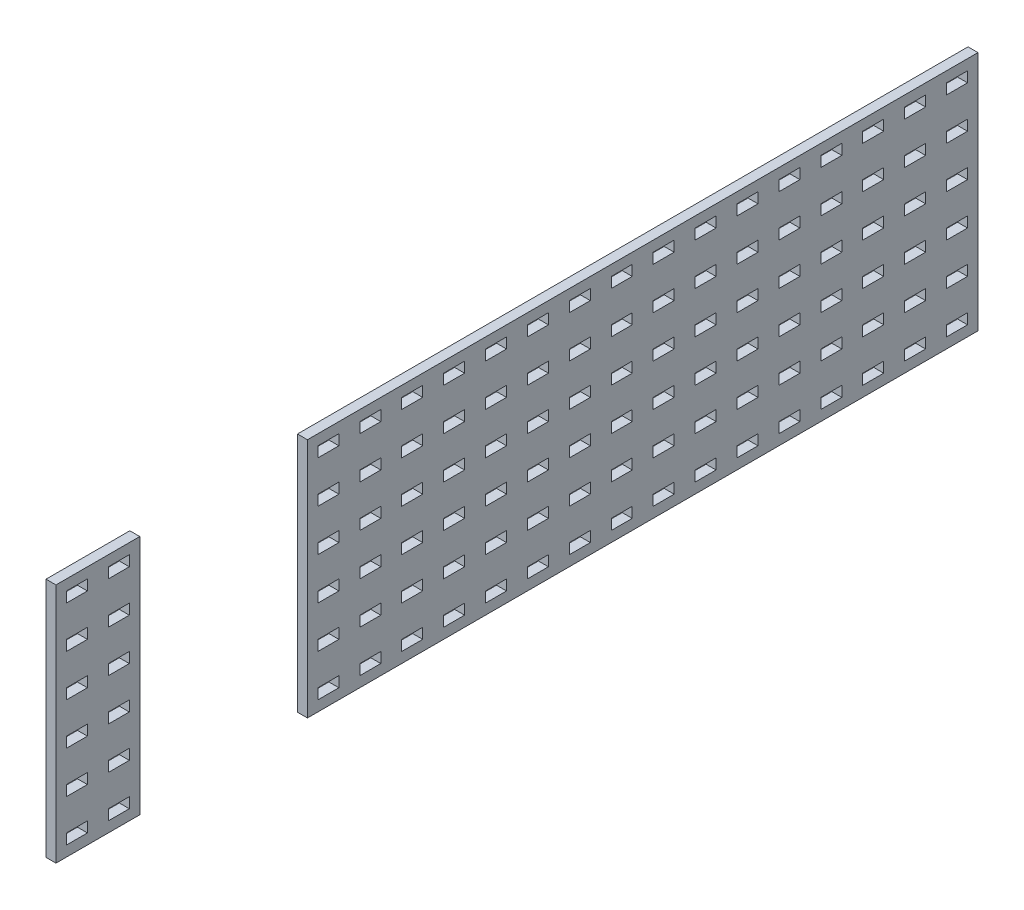
SolidWorks part; units mm, degrees
ref_plane "Front Plane" through (0, 0, 0) normal (0, 0, 1) x (1, 0, 0)
ref_plane "Top Plane" through (0, 0, 0) normal (0, 1, 0) x (1, 0, 0)
ref_plane "Right Plane" through (0, 0, 0) normal (1, 0, 0) x (0, 0, -1)
sketch "Sketch1" plane through (0, 0, 0) normal (1, 0, 0) x (0, 0, -1)
  line L1 (-279.4, -73.025) -> (279.4, -73.025)
  line L2 (-279.4, -73.025) -> (-279.4, 73.025)
  line L3 (-279.4, 73.025) -> (279.4, 73.025)
  line L4 (279.4, -73.025) -> (279.4, 73.025)
  line L5 (-279.4, -73.025) -> (279.4, 73.025) construction
  line L6 (-279.4, 73.025) -> (279.4, -73.025) construction
  point P0 (0, 0)
  dimension "D1" = 558.8
  dimension "D2" = 146.05
extrude "Boss-Extrude1" add sketch "Sketch1" along normal mid plane 6.0452
sketch "Sketch2" plane through (3.0226, 0, 0) normal (1, 0, 0) x (0, 0, -1)
  line L0 (-279.4, -73.025) -> (279.4, -73.025) construction
  line L1 (260.35, -60.325) -> (273.05, -60.325)
  line L2 (260.35, -60.325) -> (260.35, -66.675)
  line L3 (260.35, -66.675) -> (273.05, -66.675)
  line L4 (273.05, -60.325) -> (273.05, -66.675)
  line L5 (260.35, -60.325) -> (273.05, -66.675) construction
  line L6 (260.35, -66.675) -> (273.05, -60.325) construction
  line L7 (279.4, -73.025) -> (279.4, 73.025) construction
  line L8 (234.95, -66.675) -> (247.65, -66.675)
  line L9 (234.95, -60.325) -> (234.95, -66.675)
  line L10 (234.95, -60.325) -> (247.65, -60.325)
  line L11 (247.65, -60.325) -> (247.65, -66.675)
  line L12 (209.55, -66.675) -> (222.25, -66.675)
  line L13 (209.55, -60.325) -> (209.55, -66.675)
  line L14 (209.55, -60.325) -> (222.25, -60.325)
  line L15 (222.25, -60.325) -> (222.25, -66.675)
  line L16 (184.15, -66.675) -> (196.85, -66.675)
  line L17 (184.15, -60.325) -> (184.15, -66.675)
  line L18 (184.15, -60.325) -> (196.85, -60.325)
  line L19 (196.85, -60.325) -> (196.85, -66.675)
  line L20 (158.75, -66.675) -> (171.45, -66.675)
  line L21 (158.75, -60.325) -> (158.75, -66.675)
  line L22 (158.75, -60.325) -> (171.45, -60.325)
  line L23 (171.45, -60.325) -> (171.45, -66.675)
  line L24 (133.35, -66.675) -> (146.05, -66.675)
  line L25 (133.35, -60.325) -> (133.35, -66.675)
  line L26 (133.35, -60.325) -> (146.05, -60.325)
  line L27 (146.05, -60.325) -> (146.05, -66.675)
  line L28 (107.95, -66.675) -> (120.65, -66.675)
  line L29 (107.95, -60.325) -> (107.95, -66.675)
  line L30 (107.95, -60.325) -> (120.65, -60.325)
  line L31 (120.65, -60.325) -> (120.65, -66.675)
  line L32 (82.55, -66.675) -> (95.25, -66.675)
  line L33 (82.55, -60.325) -> (82.55, -66.675)
  line L34 (82.55, -60.325) -> (95.25, -60.325)
  line L35 (95.25, -60.325) -> (95.25, -66.675)
  line L36 (57.15, -66.675) -> (69.85, -66.675)
  line L37 (57.15, -60.325) -> (57.15, -66.675)
  line L38 (57.15, -60.325) -> (69.85, -60.325)
  line L39 (69.85, -60.325) -> (69.85, -66.675)
  line L40 (31.75, -66.675) -> (44.45, -66.675)
  line L41 (31.75, -60.325) -> (31.75, -66.675)
  line L42 (31.75, -60.325) -> (44.45, -60.325)
  line L43 (44.45, -60.325) -> (44.45, -66.675)
  line L44 (6.35, -66.675) -> (19.05, -66.675)
  line L45 (6.35, -60.325) -> (6.35, -66.675)
  line L46 (6.35, -60.325) -> (19.05, -60.325)
  line L47 (19.05, -60.325) -> (19.05, -66.675)
  line L48 (-19.05, -66.675) -> (-6.35, -66.675)
  line L49 (-19.05, -60.325) -> (-19.05, -66.675)
  line L50 (-19.05, -60.325) -> (-6.35, -60.325)
  line L51 (-6.35, -60.325) -> (-6.35, -66.675)
  line L52 (-44.45, -66.675) -> (-31.75, -66.675)
  line L53 (-44.45, -60.325) -> (-44.45, -66.675)
  line L54 (-44.45, -60.325) -> (-31.75, -60.325)
  line L55 (-31.75, -60.325) -> (-31.75, -66.675)
  line L56 (-69.85, -66.675) -> (-57.15, -66.675)
  line L57 (-69.85, -60.325) -> (-69.85, -66.675)
  line L58 (-69.85, -60.325) -> (-57.15, -60.325)
  line L59 (-57.15, -60.325) -> (-57.15, -66.675)
  line L60 (-95.25, -66.675) -> (-82.55, -66.675)
  line L61 (-95.25, -60.325) -> (-95.25, -66.675)
  line L62 (-95.25, -60.325) -> (-82.55, -60.325)
  line L63 (-82.55, -60.325) -> (-82.55, -66.675)
  line L64 (-120.65, -66.675) -> (-107.95, -66.675)
  line L65 (-120.65, -60.325) -> (-120.65, -66.675)
  line L66 (-120.65, -60.325) -> (-107.95, -60.325)
  line L67 (-107.95, -60.325) -> (-107.95, -66.675)
  line L68 (-146.05, -66.675) -> (-133.35, -66.675)
  line L69 (-146.05, -60.325) -> (-146.05, -66.675)
  line L70 (-146.05, -60.325) -> (-133.35, -60.325)
  line L71 (-133.35, -60.325) -> (-133.35, -66.675)
  line L72 (-171.45, -66.675) -> (-158.75, -66.675)
  line L73 (-171.45, -60.325) -> (-171.45, -66.675)
  line L74 (-171.45, -60.325) -> (-158.75, -60.325)
  line L75 (-158.75, -60.325) -> (-158.75, -66.675)
  line L76 (-196.85, -66.675) -> (-184.15, -66.675)
  line L77 (-196.85, -60.325) -> (-196.85, -66.675)
  line L78 (-196.85, -60.325) -> (-184.15, -60.325)
  line L79 (-184.15, -60.325) -> (-184.15, -66.675)
  line L80 (-222.25, -66.675) -> (-209.55, -66.675)
  line L81 (-222.25, -60.325) -> (-222.25, -66.675)
  line L82 (-222.25, -60.325) -> (-209.55, -60.325)
  line L83 (-209.55, -60.325) -> (-209.55, -66.675)
  line L84 (-247.65, -66.675) -> (-234.95, -66.675)
  line L85 (-247.65, -60.325) -> (-247.65, -66.675)
  line L86 (-247.65, -60.325) -> (-234.95, -60.325)
  line L87 (-234.95, -60.325) -> (-234.95, -66.675)
  line L88 (-273.05, -66.675) -> (-260.35, -66.675)
  line L89 (-273.05, -60.325) -> (-273.05, -66.675)
  line L90 (-273.05, -60.325) -> (-260.35, -60.325)
  line L91 (-260.35, -60.325) -> (-260.35, -66.675)
  line L92 (234.95, -41.275) -> (247.65, -41.275)
  line L93 (234.95, -34.925) -> (234.95, -41.275)
  line L94 (234.95, -34.925) -> (247.65, -34.925)
  line L95 (247.65, -34.925) -> (247.65, -41.275)
  line L96 (209.55, -41.275) -> (222.25, -41.275)
  line L97 (209.55, -34.925) -> (209.55, -41.275)
  line L98 (209.55, -34.925) -> (222.25, -34.925)
  line L99 (222.25, -34.925) -> (222.25, -41.275)
  line L100 (184.15, -41.275) -> (196.85, -41.275)
  line L101 (184.15, -34.925) -> (184.15, -41.275)
  line L102 (184.15, -34.925) -> (196.85, -34.925)
  line L103 (196.85, -34.925) -> (196.85, -41.275)
  line L104 (158.75, -41.275) -> (171.45, -41.275)
  line L105 (158.75, -34.925) -> (158.75, -41.275)
  line L106 (158.75, -34.925) -> (171.45, -34.925)
  line L107 (171.45, -34.925) -> (171.45, -41.275)
  line L108 (133.35, -41.275) -> (146.05, -41.275)
  line L109 (133.35, -34.925) -> (133.35, -41.275)
  line L110 (133.35, -34.925) -> (146.05, -34.925)
  line L111 (146.05, -34.925) -> (146.05, -41.275)
  line L112 (107.95, -41.275) -> (120.65, -41.275)
  line L113 (107.95, -34.925) -> (107.95, -41.275)
  line L114 (107.95, -34.925) -> (120.65, -34.925)
  line L115 (120.65, -34.925) -> (120.65, -41.275)
  line L116 (82.55, -41.275) -> (95.25, -41.275)
  line L117 (82.55, -34.925) -> (82.55, -41.275)
  line L118 (82.55, -34.925) -> (95.25, -34.925)
  line L119 (95.25, -34.925) -> (95.25, -41.275)
  line L120 (57.15, -41.275) -> (69.85, -41.275)
  line L121 (57.15, -34.925) -> (57.15, -41.275)
  line L122 (57.15, -34.925) -> (69.85, -34.925)
  line L123 (69.85, -34.925) -> (69.85, -41.275)
  line L124 (31.75, -41.275) -> (44.45, -41.275)
  line L125 (31.75, -34.925) -> (31.75, -41.275)
  line L126 (31.75, -34.925) -> (44.45, -34.925)
  line L127 (44.45, -34.925) -> (44.45, -41.275)
  line L128 (6.35, -41.275) -> (19.05, -41.275)
  line L129 (6.35, -34.925) -> (6.35, -41.275)
  line L130 (6.35, -34.925) -> (19.05, -34.925)
  line L131 (19.05, -34.925) -> (19.05, -41.275)
  line L132 (-19.05, -41.275) -> (-6.35, -41.275)
  line L133 (-19.05, -34.925) -> (-19.05, -41.275)
  line L134 (-19.05, -34.925) -> (-6.35, -34.925)
  line L135 (-6.35, -34.925) -> (-6.35, -41.275)
  line L136 (-44.45, -41.275) -> (-31.75, -41.275)
  line L137 (-44.45, -34.925) -> (-44.45, -41.275)
  line L138 (-44.45, -34.925) -> (-31.75, -34.925)
  line L139 (-31.75, -34.925) -> (-31.75, -41.275)
  line L140 (-69.85, -41.275) -> (-57.15, -41.275)
  line L141 (-69.85, -34.925) -> (-69.85, -41.275)
  line L142 (-69.85, -34.925) -> (-57.15, -34.925)
  line L143 (-57.15, -34.925) -> (-57.15, -41.275)
  line L144 (-95.25, -41.275) -> (-82.55, -41.275)
  line L145 (-95.25, -34.925) -> (-95.25, -41.275)
  line L146 (-95.25, -34.925) -> (-82.55, -34.925)
  line L147 (-82.55, -34.925) -> (-82.55, -41.275)
  line L148 (-120.65, -41.275) -> (-107.95, -41.275)
  line L149 (-120.65, -34.925) -> (-120.65, -41.275)
  line L150 (-120.65, -34.925) -> (-107.95, -34.925)
  line L151 (-107.95, -34.925) -> (-107.95, -41.275)
  line L152 (-146.05, -41.275) -> (-133.35, -41.275)
  line L153 (-146.05, -34.925) -> (-146.05, -41.275)
  line L154 (-146.05, -34.925) -> (-133.35, -34.925)
  line L155 (-133.35, -34.925) -> (-133.35, -41.275)
  line L156 (-171.45, -41.275) -> (-158.75, -41.275)
  line L157 (-171.45, -34.925) -> (-171.45, -41.275)
  line L158 (-171.45, -34.925) -> (-158.75, -34.925)
  line L159 (-158.75, -34.925) -> (-158.75, -41.275)
  line L160 (-196.85, -41.275) -> (-184.15, -41.275)
  line L161 (-196.85, -34.925) -> (-196.85, -41.275)
  line L162 (-196.85, -34.925) -> (-184.15, -34.925)
  line L163 (-184.15, -34.925) -> (-184.15, -41.275)
  line L164 (-222.25, -41.275) -> (-209.55, -41.275)
  line L165 (-222.25, -34.925) -> (-222.25, -41.275)
  line L166 (-222.25, -34.925) -> (-209.55, -34.925)
  line L167 (-209.55, -34.925) -> (-209.55, -41.275)
  line L168 (-247.65, -41.275) -> (-234.95, -41.275)
  line L169 (-247.65, -34.925) -> (-247.65, -41.275)
  line L170 (-247.65, -34.925) -> (-234.95, -34.925)
  line L171 (-234.95, -34.925) -> (-234.95, -41.275)
  line L172 (-273.05, -41.275) -> (-260.35, -41.275)
  line L173 (-273.05, -34.925) -> (-273.05, -41.275)
  line L174 (-273.05, -34.925) -> (-260.35, -34.925)
  line L175 (-260.35, -34.925) -> (-260.35, -41.275)
  line L176 (234.95, -15.875) -> (247.65, -15.875)
  line L177 (234.95, -9.525) -> (234.95, -15.875)
  line L178 (234.95, -9.525) -> (247.65, -9.525)
  line L179 (247.65, -9.525) -> (247.65, -15.875)
  line L180 (209.55, -15.875) -> (222.25, -15.875)
  line L181 (209.55, -9.525) -> (209.55, -15.875)
  line L182 (209.55, -9.525) -> (222.25, -9.525)
  line L183 (222.25, -9.525) -> (222.25, -15.875)
  line L184 (184.15, -15.875) -> (196.85, -15.875)
  line L185 (184.15, -9.525) -> (184.15, -15.875)
  line L186 (184.15, -9.525) -> (196.85, -9.525)
  line L187 (196.85, -9.525) -> (196.85, -15.875)
  line L188 (158.75, -15.875) -> (171.45, -15.875)
  line L189 (158.75, -9.525) -> (158.75, -15.875)
  line L190 (158.75, -9.525) -> (171.45, -9.525)
  line L191 (171.45, -9.525) -> (171.45, -15.875)
  line L192 (133.35, -15.875) -> (146.05, -15.875)
  line L193 (133.35, -9.525) -> (133.35, -15.875)
  line L194 (133.35, -9.525) -> (146.05, -9.525)
  line L195 (146.05, -9.525) -> (146.05, -15.875)
  line L196 (107.95, -15.875) -> (120.65, -15.875)
  line L197 (107.95, -9.525) -> (107.95, -15.875)
  line L198 (107.95, -9.525) -> (120.65, -9.525)
  line L199 (120.65, -9.525) -> (120.65, -15.875)
  line L200 (82.55, -15.875) -> (95.25, -15.875)
  line L201 (82.55, -9.525) -> (82.55, -15.875)
  line L202 (82.55, -9.525) -> (95.25, -9.525)
  line L203 (95.25, -9.525) -> (95.25, -15.875)
  line L204 (57.15, -15.875) -> (69.85, -15.875)
  line L205 (57.15, -9.525) -> (57.15, -15.875)
  line L206 (57.15, -9.525) -> (69.85, -9.525)
  line L207 (69.85, -9.525) -> (69.85, -15.875)
  line L208 (31.75, -15.875) -> (44.45, -15.875)
  line L209 (31.75, -9.525) -> (31.75, -15.875)
  line L210 (31.75, -9.525) -> (44.45, -9.525)
  line L211 (44.45, -9.525) -> (44.45, -15.875)
  line L212 (6.35, -15.875) -> (19.05, -15.875)
  line L213 (6.35, -9.525) -> (6.35, -15.875)
  line L214 (6.35, -9.525) -> (19.05, -9.525)
  line L215 (19.05, -9.525) -> (19.05, -15.875)
  line L216 (-19.05, -15.875) -> (-6.35, -15.875)
  line L217 (-19.05, -9.525) -> (-19.05, -15.875)
  line L218 (-19.05, -9.525) -> (-6.35, -9.525)
  line L219 (-6.35, -9.525) -> (-6.35, -15.875)
  line L220 (-44.45, -15.875) -> (-31.75, -15.875)
  line L221 (-44.45, -9.525) -> (-44.45, -15.875)
  line L222 (-44.45, -9.525) -> (-31.75, -9.525)
  line L223 (-31.75, -9.525) -> (-31.75, -15.875)
  line L224 (-69.85, -15.875) -> (-57.15, -15.875)
  line L225 (-69.85, -9.525) -> (-69.85, -15.875)
  line L226 (-69.85, -9.525) -> (-57.15, -9.525)
  line L227 (-57.15, -9.525) -> (-57.15, -15.875)
  line L228 (-95.25, -15.875) -> (-82.55, -15.875)
  line L229 (-95.25, -9.525) -> (-95.25, -15.875)
  line L230 (-95.25, -9.525) -> (-82.55, -9.525)
  line L231 (-82.55, -9.525) -> (-82.55, -15.875)
  line L232 (-120.65, -15.875) -> (-107.95, -15.875)
  line L233 (-120.65, -9.525) -> (-120.65, -15.875)
  line L234 (-120.65, -9.525) -> (-107.95, -9.525)
  line L235 (-107.95, -9.525) -> (-107.95, -15.875)
  line L236 (-146.05, -15.875) -> (-133.35, -15.875)
  line L237 (-146.05, -9.525) -> (-146.05, -15.875)
  line L238 (-146.05, -9.525) -> (-133.35, -9.525)
  line L239 (-133.35, -9.525) -> (-133.35, -15.875)
  line L240 (-171.45, -15.875) -> (-158.75, -15.875)
  line L241 (-171.45, -9.525) -> (-171.45, -15.875)
  line L242 (-171.45, -9.525) -> (-158.75, -9.525)
  line L243 (-158.75, -9.525) -> (-158.75, -15.875)
  line L244 (-196.85, -15.875) -> (-184.15, -15.875)
  line L245 (-196.85, -9.525) -> (-196.85, -15.875)
  line L246 (-196.85, -9.525) -> (-184.15, -9.525)
  line L247 (-184.15, -9.525) -> (-184.15, -15.875)
  line L248 (-222.25, -15.875) -> (-209.55, -15.875)
  line L249 (-222.25, -9.525) -> (-222.25, -15.875)
  line L250 (-222.25, -9.525) -> (-209.55, -9.525)
  line L251 (-209.55, -9.525) -> (-209.55, -15.875)
  line L252 (-247.65, -15.875) -> (-234.95, -15.875)
  line L253 (-247.65, -9.525) -> (-247.65, -15.875)
  line L254 (-247.65, -9.525) -> (-234.95, -9.525)
  line L255 (-234.95, -9.525) -> (-234.95, -15.875)
  line L256 (-273.05, -15.875) -> (-260.35, -15.875)
  line L257 (-273.05, -9.525) -> (-273.05, -15.875)
  line L258 (-273.05, -9.525) -> (-260.35, -9.525)
  line L259 (-260.35, -9.525) -> (-260.35, -15.875)
  line L260 (234.95, 9.525) -> (247.65, 9.525)
  line L261 (234.95, 15.875) -> (234.95, 9.525)
  line L262 (234.95, 15.875) -> (247.65, 15.875)
  line L263 (247.65, 15.875) -> (247.65, 9.525)
  line L264 (209.55, 9.525) -> (222.25, 9.525)
  line L265 (209.55, 15.875) -> (209.55, 9.525)
  line L266 (209.55, 15.875) -> (222.25, 15.875)
  line L267 (222.25, 15.875) -> (222.25, 9.525)
  line L268 (184.15, 9.525) -> (196.85, 9.525)
  line L269 (184.15, 15.875) -> (184.15, 9.525)
  line L270 (184.15, 15.875) -> (196.85, 15.875)
  line L271 (196.85, 15.875) -> (196.85, 9.525)
  line L272 (158.75, 9.525) -> (171.45, 9.525)
  line L273 (158.75, 15.875) -> (158.75, 9.525)
  line L274 (158.75, 15.875) -> (171.45, 15.875)
  line L275 (171.45, 15.875) -> (171.45, 9.525)
  line L276 (133.35, 9.525) -> (146.05, 9.525)
  line L277 (133.35, 15.875) -> (133.35, 9.525)
  line L278 (133.35, 15.875) -> (146.05, 15.875)
  line L279 (146.05, 15.875) -> (146.05, 9.525)
  line L280 (107.95, 9.525) -> (120.65, 9.525)
  line L281 (107.95, 15.875) -> (107.95, 9.525)
  line L282 (107.95, 15.875) -> (120.65, 15.875)
  line L283 (120.65, 15.875) -> (120.65, 9.525)
  line L284 (82.55, 9.525) -> (95.25, 9.525)
  line L285 (82.55, 15.875) -> (82.55, 9.525)
  line L286 (82.55, 15.875) -> (95.25, 15.875)
  line L287 (95.25, 15.875) -> (95.25, 9.525)
  line L288 (57.15, 9.525) -> (69.85, 9.525)
  line L289 (57.15, 15.875) -> (57.15, 9.525)
  line L290 (57.15, 15.875) -> (69.85, 15.875)
  line L291 (69.85, 15.875) -> (69.85, 9.525)
  line L292 (31.75, 9.525) -> (44.45, 9.525)
  line L293 (31.75, 15.875) -> (31.75, 9.525)
  line L294 (31.75, 15.875) -> (44.45, 15.875)
  line L295 (44.45, 15.875) -> (44.45, 9.525)
  line L296 (6.35, 9.525) -> (19.05, 9.525)
  line L297 (6.35, 15.875) -> (6.35, 9.525)
  line L298 (6.35, 15.875) -> (19.05, 15.875)
  line L299 (19.05, 15.875) -> (19.05, 9.525)
  line L300 (-19.05, 9.525) -> (-6.35, 9.525)
  line L301 (-19.05, 15.875) -> (-19.05, 9.525)
  line L302 (-19.05, 15.875) -> (-6.35, 15.875)
  line L303 (-6.35, 15.875) -> (-6.35, 9.525)
  line L304 (-44.45, 9.525) -> (-31.75, 9.525)
  line L305 (-44.45, 15.875) -> (-44.45, 9.525)
  line L306 (-44.45, 15.875) -> (-31.75, 15.875)
  line L307 (-31.75, 15.875) -> (-31.75, 9.525)
  line L308 (-69.85, 9.525) -> (-57.15, 9.525)
  line L309 (-69.85, 15.875) -> (-69.85, 9.525)
  line L310 (-69.85, 15.875) -> (-57.15, 15.875)
  line L311 (-57.15, 15.875) -> (-57.15, 9.525)
  line L312 (-95.25, 9.525) -> (-82.55, 9.525)
  line L313 (-95.25, 15.875) -> (-95.25, 9.525)
  line L314 (-95.25, 15.875) -> (-82.55, 15.875)
  line L315 (-82.55, 15.875) -> (-82.55, 9.525)
  line L316 (-120.65, 9.525) -> (-107.95, 9.525)
  line L317 (-120.65, 15.875) -> (-120.65, 9.525)
  line L318 (-120.65, 15.875) -> (-107.95, 15.875)
  line L319 (-107.95, 15.875) -> (-107.95, 9.525)
  line L320 (-146.05, 9.525) -> (-133.35, 9.525)
  line L321 (-146.05, 15.875) -> (-146.05, 9.525)
  line L322 (-146.05, 15.875) -> (-133.35, 15.875)
  line L323 (-133.35, 15.875) -> (-133.35, 9.525)
  line L324 (-171.45, 9.525) -> (-158.75, 9.525)
  line L325 (-171.45, 15.875) -> (-171.45, 9.525)
  line L326 (-171.45, 15.875) -> (-158.75, 15.875)
  line L327 (-158.75, 15.875) -> (-158.75, 9.525)
  line L328 (-196.85, 9.525) -> (-184.15, 9.525)
  line L329 (-196.85, 15.875) -> (-196.85, 9.525)
  line L330 (-196.85, 15.875) -> (-184.15, 15.875)
  line L331 (-184.15, 15.875) -> (-184.15, 9.525)
  line L332 (-222.25, 9.525) -> (-209.55, 9.525)
  line L333 (-222.25, 15.875) -> (-222.25, 9.525)
  line L334 (-222.25, 15.875) -> (-209.55, 15.875)
  line L335 (-209.55, 15.875) -> (-209.55, 9.525)
  line L336 (-247.65, 9.525) -> (-234.95, 9.525)
  line L337 (-247.65, 15.875) -> (-247.65, 9.525)
  line L338 (-247.65, 15.875) -> (-234.95, 15.875)
  line L339 (-234.95, 15.875) -> (-234.95, 9.525)
  line L340 (-273.05, 9.525) -> (-260.35, 9.525)
  line L341 (-273.05, 15.875) -> (-273.05, 9.525)
  line L342 (-273.05, 15.875) -> (-260.35, 15.875)
  line L343 (-260.35, 15.875) -> (-260.35, 9.525)
  line L344 (234.95, 34.925) -> (247.65, 34.925)
  line L345 (234.95, 41.275) -> (234.95, 34.925)
  line L346 (234.95, 41.275) -> (247.65, 41.275)
  line L347 (247.65, 41.275) -> (247.65, 34.925)
  line L348 (209.55, 34.925) -> (222.25, 34.925)
  line L349 (209.55, 41.275) -> (209.55, 34.925)
  line L350 (209.55, 41.275) -> (222.25, 41.275)
  line L351 (222.25, 41.275) -> (222.25, 34.925)
  line L352 (184.15, 34.925) -> (196.85, 34.925)
  line L353 (184.15, 41.275) -> (184.15, 34.925)
  line L354 (184.15, 41.275) -> (196.85, 41.275)
  line L355 (196.85, 41.275) -> (196.85, 34.925)
  line L356 (158.75, 34.925) -> (171.45, 34.925)
  line L357 (158.75, 41.275) -> (158.75, 34.925)
  line L358 (158.75, 41.275) -> (171.45, 41.275)
  line L359 (171.45, 41.275) -> (171.45, 34.925)
  line L360 (133.35, 34.925) -> (146.05, 34.925)
  line L361 (133.35, 41.275) -> (133.35, 34.925)
  line L362 (133.35, 41.275) -> (146.05, 41.275)
  line L363 (146.05, 41.275) -> (146.05, 34.925)
  line L364 (107.95, 34.925) -> (120.65, 34.925)
  line L365 (107.95, 41.275) -> (107.95, 34.925)
  line L366 (107.95, 41.275) -> (120.65, 41.275)
  line L367 (120.65, 41.275) -> (120.65, 34.925)
  line L368 (82.55, 34.925) -> (95.25, 34.925)
  line L369 (82.55, 41.275) -> (82.55, 34.925)
  line L370 (82.55, 41.275) -> (95.25, 41.275)
  line L371 (95.25, 41.275) -> (95.25, 34.925)
  line L372 (57.15, 34.925) -> (69.85, 34.925)
  line L373 (57.15, 41.275) -> (57.15, 34.925)
  line L374 (57.15, 41.275) -> (69.85, 41.275)
  line L375 (69.85, 41.275) -> (69.85, 34.925)
  line L376 (31.75, 34.925) -> (44.45, 34.925)
  line L377 (31.75, 41.275) -> (31.75, 34.925)
  line L378 (31.75, 41.275) -> (44.45, 41.275)
  line L379 (44.45, 41.275) -> (44.45, 34.925)
  line L380 (6.35, 34.925) -> (19.05, 34.925)
  line L381 (6.35, 41.275) -> (6.35, 34.925)
  line L382 (6.35, 41.275) -> (19.05, 41.275)
  line L383 (19.05, 41.275) -> (19.05, 34.925)
  line L384 (-19.05, 34.925) -> (-6.35, 34.925)
  line L385 (-19.05, 41.275) -> (-19.05, 34.925)
  line L386 (-19.05, 41.275) -> (-6.35, 41.275)
  line L387 (-6.35, 41.275) -> (-6.35, 34.925)
  line L388 (-44.45, 34.925) -> (-31.75, 34.925)
  line L389 (-44.45, 41.275) -> (-44.45, 34.925)
  line L390 (-44.45, 41.275) -> (-31.75, 41.275)
  line L391 (-31.75, 41.275) -> (-31.75, 34.925)
  line L392 (-69.85, 34.925) -> (-57.15, 34.925)
  line L393 (-69.85, 41.275) -> (-69.85, 34.925)
  line L394 (-69.85, 41.275) -> (-57.15, 41.275)
  line L395 (-57.15, 41.275) -> (-57.15, 34.925)
  line L396 (-95.25, 34.925) -> (-82.55, 34.925)
  line L397 (-95.25, 41.275) -> (-95.25, 34.925)
  line L398 (-95.25, 41.275) -> (-82.55, 41.275)
  line L399 (-82.55, 41.275) -> (-82.55, 34.925)
  line L400 (-120.65, 34.925) -> (-107.95, 34.925)
  line L401 (-120.65, 41.275) -> (-120.65, 34.925)
  line L402 (-120.65, 41.275) -> (-107.95, 41.275)
  line L403 (-107.95, 41.275) -> (-107.95, 34.925)
  line L404 (-146.05, 34.925) -> (-133.35, 34.925)
  line L405 (-146.05, 41.275) -> (-146.05, 34.925)
  line L406 (-146.05, 41.275) -> (-133.35, 41.275)
  line L407 (-133.35, 41.275) -> (-133.35, 34.925)
  line L408 (-171.45, 34.925) -> (-158.75, 34.925)
  line L409 (-171.45, 41.275) -> (-171.45, 34.925)
  line L410 (-171.45, 41.275) -> (-158.75, 41.275)
  line L411 (-158.75, 41.275) -> (-158.75, 34.925)
  line L412 (-196.85, 34.925) -> (-184.15, 34.925)
  line L413 (-196.85, 41.275) -> (-196.85, 34.925)
  line L414 (-196.85, 41.275) -> (-184.15, 41.275)
  line L415 (-184.15, 41.275) -> (-184.15, 34.925)
  line L416 (-222.25, 34.925) -> (-209.55, 34.925)
  line L417 (-222.25, 41.275) -> (-222.25, 34.925)
  line L418 (-222.25, 41.275) -> (-209.55, 41.275)
  line L419 (-209.55, 41.275) -> (-209.55, 34.925)
  line L420 (-247.65, 34.925) -> (-234.95, 34.925)
  line L421 (-247.65, 41.275) -> (-247.65, 34.925)
  line L422 (-247.65, 41.275) -> (-234.95, 41.275)
  line L423 (-234.95, 41.275) -> (-234.95, 34.925)
  line L424 (-273.05, 34.925) -> (-260.35, 34.925)
  line L425 (-273.05, 41.275) -> (-273.05, 34.925)
  line L426 (-273.05, 41.275) -> (-260.35, 41.275)
  line L427 (-260.35, 41.275) -> (-260.35, 34.925)
  line L428 (234.95, 60.325) -> (247.65, 60.325)
  line L429 (234.95, 66.675) -> (234.95, 60.325)
  line L430 (234.95, 66.675) -> (247.65, 66.675)
  line L431 (247.65, 66.675) -> (247.65, 60.325)
  line L432 (209.55, 60.325) -> (222.25, 60.325)
  line L433 (209.55, 66.675) -> (209.55, 60.325)
  line L434 (209.55, 66.675) -> (222.25, 66.675)
  line L435 (222.25, 66.675) -> (222.25, 60.325)
  line L436 (184.15, 60.325) -> (196.85, 60.325)
  line L437 (184.15, 66.675) -> (184.15, 60.325)
  line L438 (184.15, 66.675) -> (196.85, 66.675)
  line L439 (196.85, 66.675) -> (196.85, 60.325)
  line L440 (158.75, 60.325) -> (171.45, 60.325)
  line L441 (158.75, 66.675) -> (158.75, 60.325)
  line L442 (158.75, 66.675) -> (171.45, 66.675)
  line L443 (171.45, 66.675) -> (171.45, 60.325)
  line L444 (133.35, 60.325) -> (146.05, 60.325)
  line L445 (133.35, 66.675) -> (133.35, 60.325)
  line L446 (133.35, 66.675) -> (146.05, 66.675)
  line L447 (146.05, 66.675) -> (146.05, 60.325)
  line L448 (107.95, 60.325) -> (120.65, 60.325)
  line L449 (107.95, 66.675) -> (107.95, 60.325)
  line L450 (107.95, 66.675) -> (120.65, 66.675)
  line L451 (120.65, 66.675) -> (120.65, 60.325)
  line L452 (82.55, 60.325) -> (95.25, 60.325)
  line L453 (82.55, 66.675) -> (82.55, 60.325)
  line L454 (82.55, 66.675) -> (95.25, 66.675)
  line L455 (95.25, 66.675) -> (95.25, 60.325)
  line L456 (57.15, 60.325) -> (69.85, 60.325)
  line L457 (57.15, 66.675) -> (57.15, 60.325)
  line L458 (57.15, 66.675) -> (69.85, 66.675)
  line L459 (69.85, 66.675) -> (69.85, 60.325)
  line L460 (31.75, 60.325) -> (44.45, 60.325)
  line L461 (31.75, 66.675) -> (31.75, 60.325)
  line L462 (31.75, 66.675) -> (44.45, 66.675)
  line L463 (44.45, 66.675) -> (44.45, 60.325)
  line L464 (6.35, 60.325) -> (19.05, 60.325)
  line L465 (6.35, 66.675) -> (6.35, 60.325)
  line L466 (6.35, 66.675) -> (19.05, 66.675)
  line L467 (19.05, 66.675) -> (19.05, 60.325)
  line L468 (-19.05, 60.325) -> (-6.35, 60.325)
  line L469 (-19.05, 66.675) -> (-19.05, 60.325)
  line L470 (-19.05, 66.675) -> (-6.35, 66.675)
  line L471 (-6.35, 66.675) -> (-6.35, 60.325)
  line L472 (-44.45, 60.325) -> (-31.75, 60.325)
  line L473 (-44.45, 66.675) -> (-44.45, 60.325)
  line L474 (-44.45, 66.675) -> (-31.75, 66.675)
  line L475 (-31.75, 66.675) -> (-31.75, 60.325)
  line L476 (-69.85, 60.325) -> (-57.15, 60.325)
  line L477 (-69.85, 66.675) -> (-69.85, 60.325)
  line L478 (-69.85, 66.675) -> (-57.15, 66.675)
  line L479 (-57.15, 66.675) -> (-57.15, 60.325)
  line L480 (-95.25, 60.325) -> (-82.55, 60.325)
  line L481 (-95.25, 66.675) -> (-95.25, 60.325)
  line L482 (-95.25, 66.675) -> (-82.55, 66.675)
  line L483 (-82.55, 66.675) -> (-82.55, 60.325)
  line L484 (-120.65, 60.325) -> (-107.95, 60.325)
  line L485 (-120.65, 66.675) -> (-120.65, 60.325)
  line L486 (-120.65, 66.675) -> (-107.95, 66.675)
  line L487 (-107.95, 66.675) -> (-107.95, 60.325)
  line L488 (-146.05, 60.325) -> (-133.35, 60.325)
  line L489 (-146.05, 66.675) -> (-146.05, 60.325)
  line L490 (-146.05, 66.675) -> (-133.35, 66.675)
  line L491 (-133.35, 66.675) -> (-133.35, 60.325)
  line L492 (-171.45, 60.325) -> (-158.75, 60.325)
  line L493 (-171.45, 66.675) -> (-171.45, 60.325)
  line L494 (-171.45, 66.675) -> (-158.75, 66.675)
  line L495 (-158.75, 66.675) -> (-158.75, 60.325)
  line L496 (-196.85, 60.325) -> (-184.15, 60.325)
  line L497 (-196.85, 66.675) -> (-196.85, 60.325)
  line L498 (-196.85, 66.675) -> (-184.15, 66.675)
  line L499 (-184.15, 66.675) -> (-184.15, 60.325)
  line L500 (-222.25, 60.325) -> (-209.55, 60.325)
  line L501 (-222.25, 66.675) -> (-222.25, 60.325)
  line L502 (-222.25, 66.675) -> (-209.55, 66.675)
  line L503 (-209.55, 66.675) -> (-209.55, 60.325)
  line L504 (-247.65, 60.325) -> (-234.95, 60.325)
  line L505 (-247.65, 66.675) -> (-247.65, 60.325)
  line L506 (-247.65, 66.675) -> (-234.95, 66.675)
  line L507 (-234.95, 66.675) -> (-234.95, 60.325)
  line L508 (-273.05, 60.325) -> (-260.35, 60.325)
  line L509 (-273.05, 66.675) -> (-273.05, 60.325)
  line L510 (-273.05, 66.675) -> (-260.35, 66.675)
  line L511 (-260.35, 66.675) -> (-260.35, 60.325)
  line L512 (234.95, 85.725) -> (247.65, 85.725)
  line L513 (234.95, 92.075) -> (234.95, 85.725)
  line L514 (234.95, 92.075) -> (247.65, 92.075)
  line L515 (247.65, 92.075) -> (247.65, 85.725)
  line L516 (209.55, 85.725) -> (222.25, 85.725)
  line L517 (209.55, 92.075) -> (209.55, 85.725)
  line L518 (209.55, 92.075) -> (222.25, 92.075)
  line L519 (222.25, 92.075) -> (222.25, 85.725)
  line L520 (184.15, 85.725) -> (196.85, 85.725)
  line L521 (184.15, 92.075) -> (184.15, 85.725)
  line L522 (184.15, 92.075) -> (196.85, 92.075)
  line L523 (196.85, 92.075) -> (196.85, 85.725)
  line L524 (158.75, 85.725) -> (171.45, 85.725)
  line L525 (158.75, 92.075) -> (158.75, 85.725)
  line L526 (158.75, 92.075) -> (171.45, 92.075)
  line L527 (171.45, 92.075) -> (171.45, 85.725)
  line L528 (133.35, 85.725) -> (146.05, 85.725)
  line L529 (133.35, 92.075) -> (133.35, 85.725)
  line L530 (133.35, 92.075) -> (146.05, 92.075)
  line L531 (146.05, 92.075) -> (146.05, 85.725)
  line L532 (107.95, 85.725) -> (120.65, 85.725)
  line L533 (107.95, 92.075) -> (107.95, 85.725)
  line L534 (107.95, 92.075) -> (120.65, 92.075)
  line L535 (120.65, 92.075) -> (120.65, 85.725)
  line L536 (82.55, 85.725) -> (95.25, 85.725)
  line L537 (82.55, 92.075) -> (82.55, 85.725)
  line L538 (82.55, 92.075) -> (95.25, 92.075)
  line L539 (95.25, 92.075) -> (95.25, 85.725)
  line L540 (57.15, 85.725) -> (69.85, 85.725)
  line L541 (57.15, 92.075) -> (57.15, 85.725)
  line L542 (57.15, 92.075) -> (69.85, 92.075)
  line L543 (69.85, 92.075) -> (69.85, 85.725)
  line L544 (31.75, 85.725) -> (44.45, 85.725)
  line L545 (31.75, 92.075) -> (31.75, 85.725)
  line L546 (31.75, 92.075) -> (44.45, 92.075)
  line L547 (44.45, 92.075) -> (44.45, 85.725)
  line L548 (6.35, 85.725) -> (19.05, 85.725)
  line L549 (6.35, 92.075) -> (6.35, 85.725)
  line L550 (6.35, 92.075) -> (19.05, 92.075)
  line L551 (19.05, 92.075) -> (19.05, 85.725)
  line L552 (-19.05, 85.725) -> (-6.35, 85.725)
  line L553 (-19.05, 92.075) -> (-19.05, 85.725)
  line L554 (-19.05, 92.075) -> (-6.35, 92.075)
  line L555 (-6.35, 92.075) -> (-6.35, 85.725)
  line L556 (-44.45, 85.725) -> (-31.75, 85.725)
  line L557 (-44.45, 92.075) -> (-44.45, 85.725)
  line L558 (-44.45, 92.075) -> (-31.75, 92.075)
  line L559 (-31.75, 92.075) -> (-31.75, 85.725)
  line L560 (-69.85, 85.725) -> (-57.15, 85.725)
  line L561 (-69.85, 92.075) -> (-69.85, 85.725)
  line L562 (-69.85, 92.075) -> (-57.15, 92.075)
  line L563 (-57.15, 92.075) -> (-57.15, 85.725)
  line L564 (-95.25, 85.725) -> (-82.55, 85.725)
  line L565 (-95.25, 92.075) -> (-95.25, 85.725)
  line L566 (-95.25, 92.075) -> (-82.55, 92.075)
  line L567 (-82.55, 92.075) -> (-82.55, 85.725)
  line L568 (-120.65, 85.725) -> (-107.95, 85.725)
  line L569 (-120.65, 92.075) -> (-120.65, 85.725)
  line L570 (-120.65, 92.075) -> (-107.95, 92.075)
  line L571 (-107.95, 92.075) -> (-107.95, 85.725)
  line L572 (-146.05, 85.725) -> (-133.35, 85.725)
  line L573 (-146.05, 92.075) -> (-146.05, 85.725)
  line L574 (-146.05, 92.075) -> (-133.35, 92.075)
  line L575 (-133.35, 92.075) -> (-133.35, 85.725)
  line L576 (-171.45, 85.725) -> (-158.75, 85.725)
  line L577 (-171.45, 92.075) -> (-171.45, 85.725)
  line L578 (-171.45, 92.075) -> (-158.75, 92.075)
  line L579 (-158.75, 92.075) -> (-158.75, 85.725)
  line L580 (-196.85, 85.725) -> (-184.15, 85.725)
  line L581 (-196.85, 92.075) -> (-196.85, 85.725)
  line L582 (-196.85, 92.075) -> (-184.15, 92.075)
  line L583 (-184.15, 92.075) -> (-184.15, 85.725)
  line L584 (-222.25, 85.725) -> (-209.55, 85.725)
  line L585 (-222.25, 92.075) -> (-222.25, 85.725)
  line L586 (-222.25, 92.075) -> (-209.55, 92.075)
  line L587 (-209.55, 92.075) -> (-209.55, 85.725)
  line L588 (-247.65, 85.725) -> (-234.95, 85.725)
  line L589 (-247.65, 92.075) -> (-247.65, 85.725)
  line L590 (-247.65, 92.075) -> (-234.95, 92.075)
  line L591 (-234.95, 92.075) -> (-234.95, 85.725)
  line L592 (-273.05, 85.725) -> (-260.35, 85.725)
  line L593 (-273.05, 92.075) -> (-273.05, 85.725)
  line L594 (-273.05, 92.075) -> (-260.35, 92.075)
  line L595 (-260.35, 92.075) -> (-260.35, 85.725)
  line L596 (234.95, 111.125) -> (247.65, 111.125)
  line L597 (234.95, 117.475) -> (234.95, 111.125)
  line L598 (234.95, 117.475) -> (247.65, 117.475)
  line L599 (247.65, 117.475) -> (247.65, 111.125)
  line L600 (209.55, 111.125) -> (222.25, 111.125)
  line L601 (209.55, 117.475) -> (209.55, 111.125)
  line L602 (209.55, 117.475) -> (222.25, 117.475)
  line L603 (222.25, 117.475) -> (222.25, 111.125)
  line L604 (184.15, 111.125) -> (196.85, 111.125)
  line L605 (184.15, 117.475) -> (184.15, 111.125)
  line L606 (184.15, 117.475) -> (196.85, 117.475)
  line L607 (196.85, 117.475) -> (196.85, 111.125)
  line L608 (158.75, 111.125) -> (171.45, 111.125)
  line L609 (158.75, 117.475) -> (158.75, 111.125)
  line L610 (158.75, 117.475) -> (171.45, 117.475)
  line L611 (171.45, 117.475) -> (171.45, 111.125)
  line L612 (133.35, 111.125) -> (146.05, 111.125)
  line L613 (133.35, 117.475) -> (133.35, 111.125)
  line L614 (133.35, 117.475) -> (146.05, 117.475)
  line L615 (146.05, 117.475) -> (146.05, 111.125)
  line L616 (107.95, 111.125) -> (120.65, 111.125)
  line L617 (107.95, 117.475) -> (107.95, 111.125)
  line L618 (107.95, 117.475) -> (120.65, 117.475)
  line L619 (120.65, 117.475) -> (120.65, 111.125)
  line L620 (82.55, 111.125) -> (95.25, 111.125)
  line L621 (82.55, 117.475) -> (82.55, 111.125)
  line L622 (82.55, 117.475) -> (95.25, 117.475)
  line L623 (95.25, 117.475) -> (95.25, 111.125)
  line L624 (57.15, 111.125) -> (69.85, 111.125)
  line L625 (57.15, 117.475) -> (57.15, 111.125)
  line L626 (57.15, 117.475) -> (69.85, 117.475)
  line L627 (69.85, 117.475) -> (69.85, 111.125)
  line L628 (31.75, 111.125) -> (44.45, 111.125)
  line L629 (31.75, 117.475) -> (31.75, 111.125)
  line L630 (31.75, 117.475) -> (44.45, 117.475)
  line L631 (44.45, 117.475) -> (44.45, 111.125)
  line L632 (6.35, 111.125) -> (19.05, 111.125)
  line L633 (6.35, 117.475) -> (6.35, 111.125)
  line L634 (6.35, 117.475) -> (19.05, 117.475)
  line L635 (19.05, 117.475) -> (19.05, 111.125)
  line L636 (-19.05, 111.125) -> (-6.35, 111.125)
  line L637 (-19.05, 117.475) -> (-19.05, 111.125)
  line L638 (-19.05, 117.475) -> (-6.35, 117.475)
  line L639 (-6.35, 117.475) -> (-6.35, 111.125)
  line L640 (-44.45, 111.125) -> (-31.75, 111.125)
  line L641 (-44.45, 117.475) -> (-44.45, 111.125)
  line L642 (-44.45, 117.475) -> (-31.75, 117.475)
  line L643 (-31.75, 117.475) -> (-31.75, 111.125)
  line L644 (-69.85, 111.125) -> (-57.15, 111.125)
  line L645 (-69.85, 117.475) -> (-69.85, 111.125)
  line L646 (-69.85, 117.475) -> (-57.15, 117.475)
  line L647 (-57.15, 117.475) -> (-57.15, 111.125)
  line L648 (-95.25, 111.125) -> (-82.55, 111.125)
  line L649 (-95.25, 117.475) -> (-95.25, 111.125)
  line L650 (-95.25, 117.475) -> (-82.55, 117.475)
  line L651 (-82.55, 117.475) -> (-82.55, 111.125)
  line L652 (-120.65, 111.125) -> (-107.95, 111.125)
  line L653 (-120.65, 117.475) -> (-120.65, 111.125)
  line L654 (-120.65, 117.475) -> (-107.95, 117.475)
  line L655 (-107.95, 117.475) -> (-107.95, 111.125)
  line L656 (-146.05, 111.125) -> (-133.35, 111.125)
  line L657 (-146.05, 117.475) -> (-146.05, 111.125)
  line L658 (-146.05, 117.475) -> (-133.35, 117.475)
  line L659 (-133.35, 117.475) -> (-133.35, 111.125)
  line L660 (-171.45, 111.125) -> (-158.75, 111.125)
  line L661 (-171.45, 117.475) -> (-171.45, 111.125)
  line L662 (-171.45, 117.475) -> (-158.75, 117.475)
  line L663 (-158.75, 117.475) -> (-158.75, 111.125)
  line L664 (-196.85, 111.125) -> (-184.15, 111.125)
  line L665 (-196.85, 117.475) -> (-196.85, 111.125)
  line L666 (-196.85, 117.475) -> (-184.15, 117.475)
  line L667 (-184.15, 117.475) -> (-184.15, 111.125)
  line L668 (-222.25, 111.125) -> (-209.55, 111.125)
  line L669 (-222.25, 117.475) -> (-222.25, 111.125)
  line L670 (-222.25, 117.475) -> (-209.55, 117.475)
  line L671 (-209.55, 117.475) -> (-209.55, 111.125)
  line L672 (-247.65, 111.125) -> (-234.95, 111.125)
  line L673 (-247.65, 117.475) -> (-247.65, 111.125)
  line L674 (-247.65, 117.475) -> (-234.95, 117.475)
  line L675 (-234.95, 117.475) -> (-234.95, 111.125)
  line L676 (-273.05, 111.125) -> (-260.35, 111.125)
  line L677 (-273.05, 117.475) -> (-273.05, 111.125)
  line L678 (-273.05, 117.475) -> (-260.35, 117.475)
  line L679 (-260.35, 117.475) -> (-260.35, 111.125)
  line L680 (234.95, 136.525) -> (247.65, 136.525)
  line L681 (234.95, 142.875) -> (234.95, 136.525)
  line L682 (234.95, 142.875) -> (247.65, 142.875)
  line L683 (247.65, 142.875) -> (247.65, 136.525)
  line L684 (209.55, 136.525) -> (222.25, 136.525)
  line L685 (209.55, 142.875) -> (209.55, 136.525)
  line L686 (209.55, 142.875) -> (222.25, 142.875)
  line L687 (222.25, 142.875) -> (222.25, 136.525)
  line L688 (184.15, 136.525) -> (196.85, 136.525)
  line L689 (184.15, 142.875) -> (184.15, 136.525)
  line L690 (184.15, 142.875) -> (196.85, 142.875)
  line L691 (196.85, 142.875) -> (196.85, 136.525)
  line L692 (158.75, 136.525) -> (171.45, 136.525)
  line L693 (158.75, 142.875) -> (158.75, 136.525)
  line L694 (158.75, 142.875) -> (171.45, 142.875)
  line L695 (171.45, 142.875) -> (171.45, 136.525)
  line L696 (133.35, 136.525) -> (146.05, 136.525)
  line L697 (133.35, 142.875) -> (133.35, 136.525)
  line L698 (133.35, 142.875) -> (146.05, 142.875)
  line L699 (146.05, 142.875) -> (146.05, 136.525)
  line L700 (107.95, 136.525) -> (120.65, 136.525)
  line L701 (107.95, 142.875) -> (107.95, 136.525)
  line L702 (107.95, 142.875) -> (120.65, 142.875)
  line L703 (120.65, 142.875) -> (120.65, 136.525)
  line L704 (82.55, 136.525) -> (95.25, 136.525)
  line L705 (82.55, 142.875) -> (82.55, 136.525)
  line L706 (82.55, 142.875) -> (95.25, 142.875)
  line L707 (95.25, 142.875) -> (95.25, 136.525)
  line L708 (57.15, 136.525) -> (69.85, 136.525)
  line L709 (57.15, 142.875) -> (57.15, 136.525)
  line L710 (57.15, 142.875) -> (69.85, 142.875)
  line L711 (69.85, 142.875) -> (69.85, 136.525)
  line L712 (31.75, 136.525) -> (44.45, 136.525)
  line L713 (31.75, 142.875) -> (31.75, 136.525)
  line L714 (31.75, 142.875) -> (44.45, 142.875)
  line L715 (44.45, 142.875) -> (44.45, 136.525)
  line L716 (6.35, 136.525) -> (19.05, 136.525)
  line L717 (6.35, 142.875) -> (6.35, 136.525)
  line L718 (6.35, 142.875) -> (19.05, 142.875)
  line L719 (19.05, 142.875) -> (19.05, 136.525)
  line L720 (-19.05, 136.525) -> (-6.35, 136.525)
  line L721 (-19.05, 142.875) -> (-19.05, 136.525)
  line L722 (-19.05, 142.875) -> (-6.35, 142.875)
  line L723 (-6.35, 142.875) -> (-6.35, 136.525)
  line L724 (-44.45, 136.525) -> (-31.75, 136.525)
  line L725 (-44.45, 142.875) -> (-44.45, 136.525)
  line L726 (-44.45, 142.875) -> (-31.75, 142.875)
  line L727 (-31.75, 142.875) -> (-31.75, 136.525)
  line L728 (-69.85, 136.525) -> (-57.15, 136.525)
  line L729 (-69.85, 142.875) -> (-69.85, 136.525)
  line L730 (-69.85, 142.875) -> (-57.15, 142.875)
  line L731 (-57.15, 142.875) -> (-57.15, 136.525)
  line L732 (-95.25, 136.525) -> (-82.55, 136.525)
  line L733 (-95.25, 142.875) -> (-95.25, 136.525)
  line L734 (-95.25, 142.875) -> (-82.55, 142.875)
  line L735 (-82.55, 142.875) -> (-82.55, 136.525)
  line L736 (-120.65, 136.525) -> (-107.95, 136.525)
  line L737 (-120.65, 142.875) -> (-120.65, 136.525)
  line L738 (-120.65, 142.875) -> (-107.95, 142.875)
  line L739 (-107.95, 142.875) -> (-107.95, 136.525)
  line L740 (-146.05, 136.525) -> (-133.35, 136.525)
  line L741 (-146.05, 142.875) -> (-146.05, 136.525)
  line L742 (-146.05, 142.875) -> (-133.35, 142.875)
  line L743 (-133.35, 142.875) -> (-133.35, 136.525)
  line L744 (-171.45, 136.525) -> (-158.75, 136.525)
  line L745 (-171.45, 142.875) -> (-171.45, 136.525)
  line L746 (-171.45, 142.875) -> (-158.75, 142.875)
  line L747 (-158.75, 142.875) -> (-158.75, 136.525)
  line L748 (-196.85, 136.525) -> (-184.15, 136.525)
  line L749 (-196.85, 142.875) -> (-196.85, 136.525)
  line L750 (-196.85, 142.875) -> (-184.15, 142.875)
  line L751 (-184.15, 142.875) -> (-184.15, 136.525)
  line L752 (-222.25, 136.525) -> (-209.55, 136.525)
  line L753 (-222.25, 142.875) -> (-222.25, 136.525)
  line L754 (-222.25, 142.875) -> (-209.55, 142.875)
  line L755 (-209.55, 142.875) -> (-209.55, 136.525)
  line L756 (-247.65, 136.525) -> (-234.95, 136.525)
  line L757 (-247.65, 142.875) -> (-247.65, 136.525)
  line L758 (-247.65, 142.875) -> (-234.95, 142.875)
  line L759 (-234.95, 142.875) -> (-234.95, 136.525)
  line L760 (-273.05, 136.525) -> (-260.35, 136.525)
  line L761 (-273.05, 142.875) -> (-273.05, 136.525)
  line L762 (-273.05, 142.875) -> (-260.35, 142.875)
  line L763 (-260.35, 142.875) -> (-260.35, 136.525)
  line L764 (234.95, 161.925) -> (247.65, 161.925)
  line L765 (234.95, 168.275) -> (234.95, 161.925)
  line L766 (234.95, 168.275) -> (247.65, 168.275)
  line L767 (247.65, 168.275) -> (247.65, 161.925)
  line L768 (209.55, 161.925) -> (222.25, 161.925)
  line L769 (209.55, 168.275) -> (209.55, 161.925)
  line L770 (209.55, 168.275) -> (222.25, 168.275)
  line L771 (222.25, 168.275) -> (222.25, 161.925)
  line L772 (184.15, 161.925) -> (196.85, 161.925)
  line L773 (184.15, 168.275) -> (184.15, 161.925)
  line L774 (184.15, 168.275) -> (196.85, 168.275)
  line L775 (196.85, 168.275) -> (196.85, 161.925)
  line L776 (158.75, 161.925) -> (171.45, 161.925)
  line L777 (158.75, 168.275) -> (158.75, 161.925)
  line L778 (158.75, 168.275) -> (171.45, 168.275)
  line L779 (171.45, 168.275) -> (171.45, 161.925)
  line L780 (133.35, 161.925) -> (146.05, 161.925)
  line L781 (133.35, 168.275) -> (133.35, 161.925)
  line L782 (133.35, 168.275) -> (146.05, 168.275)
  line L783 (146.05, 168.275) -> (146.05, 161.925)
  line L784 (107.95, 161.925) -> (120.65, 161.925)
  line L785 (107.95, 168.275) -> (107.95, 161.925)
  line L786 (107.95, 168.275) -> (120.65, 168.275)
  line L787 (120.65, 168.275) -> (120.65, 161.925)
  line L788 (82.55, 161.925) -> (95.25, 161.925)
  line L789 (82.55, 168.275) -> (82.55, 161.925)
  line L790 (82.55, 168.275) -> (95.25, 168.275)
  line L791 (95.25, 168.275) -> (95.25, 161.925)
  line L792 (57.15, 161.925) -> (69.85, 161.925)
  line L793 (57.15, 168.275) -> (57.15, 161.925)
  line L794 (57.15, 168.275) -> (69.85, 168.275)
  line L795 (69.85, 168.275) -> (69.85, 161.925)
  line L796 (31.75, 161.925) -> (44.45, 161.925)
  line L797 (31.75, 168.275) -> (31.75, 161.925)
  line L798 (31.75, 168.275) -> (44.45, 168.275)
  line L799 (44.45, 168.275) -> (44.45, 161.925)
  line L800 (6.35, 161.925) -> (19.05, 161.925)
  line L801 (6.35, 168.275) -> (6.35, 161.925)
  line L802 (6.35, 168.275) -> (19.05, 168.275)
  line L803 (19.05, 168.275) -> (19.05, 161.925)
  line L804 (-19.05, 161.925) -> (-6.35, 161.925)
  line L805 (-19.05, 168.275) -> (-19.05, 161.925)
  line L806 (-19.05, 168.275) -> (-6.35, 168.275)
  line L807 (-6.35, 168.275) -> (-6.35, 161.925)
  line L808 (-44.45, 161.925) -> (-31.75, 161.925)
  line L809 (-44.45, 168.275) -> (-44.45, 161.925)
  line L810 (-44.45, 168.275) -> (-31.75, 168.275)
  line L811 (-31.75, 168.275) -> (-31.75, 161.925)
  line L812 (-69.85, 161.925) -> (-57.15, 161.925)
  line L813 (-69.85, 168.275) -> (-69.85, 161.925)
  line L814 (-69.85, 168.275) -> (-57.15, 168.275)
  line L815 (-57.15, 168.275) -> (-57.15, 161.925)
  line L816 (-95.25, 161.925) -> (-82.55, 161.925)
  line L817 (-95.25, 168.275) -> (-95.25, 161.925)
  line L818 (-95.25, 168.275) -> (-82.55, 168.275)
  line L819 (-82.55, 168.275) -> (-82.55, 161.925)
  line L820 (-120.65, 161.925) -> (-107.95, 161.925)
  line L821 (-120.65, 168.275) -> (-120.65, 161.925)
  line L822 (-120.65, 168.275) -> (-107.95, 168.275)
  line L823 (-107.95, 168.275) -> (-107.95, 161.925)
  line L824 (-146.05, 161.925) -> (-133.35, 161.925)
  line L825 (-146.05, 168.275) -> (-146.05, 161.925)
  line L826 (-146.05, 168.275) -> (-133.35, 168.275)
  line L827 (-133.35, 168.275) -> (-133.35, 161.925)
  line L828 (-171.45, 161.925) -> (-158.75, 161.925)
  line L829 (-171.45, 168.275) -> (-171.45, 161.925)
  line L830 (-171.45, 168.275) -> (-158.75, 168.275)
  line L831 (-158.75, 168.275) -> (-158.75, 161.925)
  line L832 (-196.85, 161.925) -> (-184.15, 161.925)
  line L833 (-196.85, 168.275) -> (-196.85, 161.925)
  line L834 (-196.85, 168.275) -> (-184.15, 168.275)
  line L835 (-184.15, 168.275) -> (-184.15, 161.925)
  line L836 (-222.25, 161.925) -> (-209.55, 161.925)
  line L837 (-222.25, 168.275) -> (-222.25, 161.925)
  line L838 (-222.25, 168.275) -> (-209.55, 168.275)
  line L839 (-209.55, 168.275) -> (-209.55, 161.925)
  line L840 (-247.65, 161.925) -> (-234.95, 161.925)
  line L841 (-247.65, 168.275) -> (-247.65, 161.925)
  line L842 (-247.65, 168.275) -> (-234.95, 168.275)
  line L843 (-234.95, 168.275) -> (-234.95, 161.925)
  line L844 (-273.05, 161.925) -> (-260.35, 161.925)
  line L845 (-273.05, 168.275) -> (-273.05, 161.925)
  line L846 (-273.05, 168.275) -> (-260.35, 168.275)
  line L847 (-260.35, 168.275) -> (-260.35, 161.925)
  line L848 (260.35, -41.275) -> (273.05, -41.275)
  line L849 (260.35, -34.925) -> (260.35, -41.275)
  line L850 (260.35, -34.925) -> (273.05, -34.925)
  line L851 (273.05, -34.925) -> (273.05, -41.275)
  line L852 (260.35, -15.875) -> (273.05, -15.875)
  line L853 (260.35, -9.525) -> (260.35, -15.875)
  line L854 (260.35, -9.525) -> (273.05, -9.525)
  line L855 (273.05, -9.525) -> (273.05, -15.875)
  line L856 (260.35, 9.525) -> (273.05, 9.525)
  line L857 (260.35, 15.875) -> (260.35, 9.525)
  line L858 (260.35, 15.875) -> (273.05, 15.875)
  line L859 (273.05, 15.875) -> (273.05, 9.525)
  line L860 (260.35, 34.925) -> (273.05, 34.925)
  line L861 (260.35, 41.275) -> (260.35, 34.925)
  line L862 (260.35, 41.275) -> (273.05, 41.275)
  line L863 (273.05, 41.275) -> (273.05, 34.925)
  line L864 (260.35, 60.325) -> (273.05, 60.325)
  line L865 (260.35, 66.675) -> (260.35, 60.325)
  line L866 (260.35, 66.675) -> (273.05, 66.675)
  line L867 (273.05, 66.675) -> (273.05, 60.325)
  line L868 (260.35, 85.725) -> (273.05, 85.725)
  line L869 (260.35, 92.075) -> (260.35, 85.725)
  line L870 (260.35, 92.075) -> (273.05, 92.075)
  line L871 (273.05, 92.075) -> (273.05, 85.725)
  line L872 (260.35, 111.125) -> (273.05, 111.125)
  line L873 (260.35, 117.475) -> (260.35, 111.125)
  line L874 (260.35, 117.475) -> (273.05, 117.475)
  line L875 (273.05, 117.475) -> (273.05, 111.125)
  line L876 (260.35, 136.525) -> (273.05, 136.525)
  line L877 (260.35, 142.875) -> (260.35, 136.525)
  line L878 (260.35, 142.875) -> (273.05, 142.875)
  line L879 (273.05, 142.875) -> (273.05, 136.525)
  line L880 (260.35, 161.925) -> (273.05, 161.925)
  line L881 (260.35, 168.275) -> (260.35, 161.925)
  line L882 (260.35, 168.275) -> (273.05, 168.275)
  line L883 (273.05, 168.275) -> (273.05, 161.925)
  point P0 (266.7, -63.5)
  dimension "D1" = 6.35
  dimension "D2" = 12.7
  dimension "D3" = 9.525
  dimension "D4" = 12.7
  dimension "D5" = 22
  dimension "D6" = 10
extrude "Cut-Extrude1" cut sketch "Sketch2" against normal through all
sketch "Sketch3" plane through (3.0226, 0, 0) normal (1, 0, 0) x (0, 0, -1)
  line L0 (279.4, 73.025) -> (-279.4, 73.025) construction
  line L1 (-127, 73.025) -> (-228.6, 73.025)
  line L2 (-127, 73.025) -> (-127, -73.025)
  line L3 (-127, -73.025) -> (-228.6, -73.025)
  line L4 (-228.6, 73.025) -> (-228.6, -73.025)
  line L5 (-279.4, -73.025) -> (279.4, -73.025) construction
  line L8 (-234.95, 60.325) -> (-234.95, 66.675) construction
  line L9 (-120.65, 66.675) -> (-120.65, 60.325) construction
  dimension "D1" = 6.35
  dimension "D2" = 6.35
extrude "Cut-Extrude2" cut sketch "Sketch3" against normal through all
